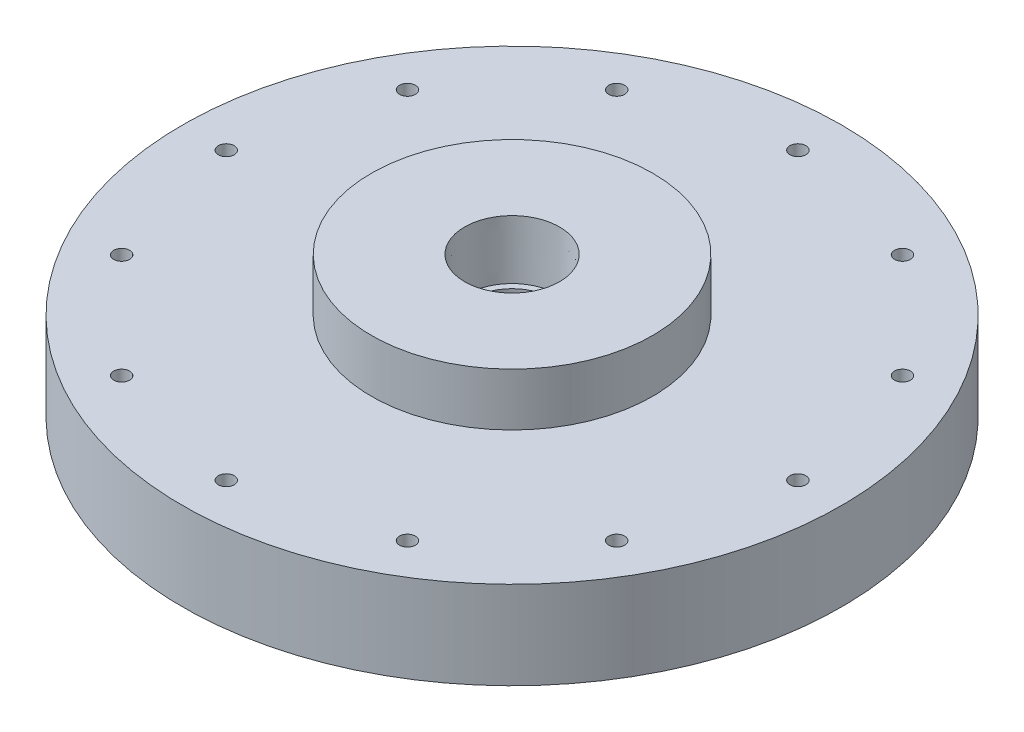
SolidWorks part; units mm, degrees
material "7075-T6 (SN)"
ref_plane "Front Plane" through (0, 0, 0) normal (0, 0, 1) x (1, 0, 0)
ref_plane "Top Plane" through (0, 0, 0) normal (0, 1, 0) x (1, 0, 0)
ref_plane "Right Plane" through (0, 0, 0) normal (1, 0, 0) x (0, 0, -1)
sketch "Sketch2" plane through (0, 0, 0) normal (0, 1, 0) x (1, 0, 0)
  circle A1 centre (0, 0) radius 25.4
  dimension "D1" = 50.8
extrude "Base Cylinder" add sketch "Sketch2" along normal blind 19.05
sketch "Sketch3" plane through (0, 0, 0) normal (0, -1, 0) x (1, 0, 0)
  circle A1 centre (0, 0) radius 59.5312
  dimension "D1" = 119.0625
extrude "Aft Flange" add sketch "Sketch3" against normal blind 9.525
sketch "Sketch For Bolt Holes" plane through (0, 0, 0) normal (0, -1, 0) x (1, 0, 0)
  circle A0 centre (-51.6255, 0) radius 1.5875
  circle A1 centre (-44.709, 25.8128) radius 1.5875
  circle A2 centre (-25.8128, 44.709) radius 1.5875
  circle A3 centre (0, 51.6255) radius 1.5875
  circle A4 centre (25.8127, 44.709) radius 1.5875
  circle A5 centre (44.709, 25.8128) radius 1.5875
  circle A6 centre (51.6255, 0) radius 1.5875
  circle A7 centre (44.709, -25.8127) radius 1.5875
  circle A8 centre (25.8128, -44.709) radius 1.5875
  circle A9 centre (0, -51.6255) radius 1.5875
  circle A10 centre (-25.8127, -44.709) radius 1.5875
  circle A11 centre (-44.709, -25.8128) radius 1.5875
  point P36 (0, 0)
  dimension "D2" = 3.175
  dimension "D1" = 51.6255
  dimension "D3" = 12
hole_wizard "Bolt Circle" positions "Sketch8" profile "Sketch9" hole size "#4-40" standard "ANSI Inch" end condition up to next
sketch "Sketch8" plane through (0, 0, 0) normal (0, -1, 0) x (-1, 0, 0)
  point P0 (-25.8127, -44.709)
  point P3 (-44.709, -25.8128)
  point P6 (-51.6255, 0)
  point P9 (-44.709, 25.8127)
  point P12 (-25.8128, 44.709)
  point P15 (0, 51.6255)
  point P18 (25.8127, 44.709)
  point P21 (44.709, 25.8128)
  point P24 (51.6255, 0)
  point P27 (44.709, -25.8128)
  point P30 (25.8128, -44.709)
  point P33 (0, -51.6255)
  point P36 (-25.8127, -44.709)
  point P38 (-44.709, -25.8128)
  point P40 (-51.6255, 0)
sketch "Sketch9" plane through (25.8127, 0, 44.709) normal (1, 0, 0) x (0, 0, -1)
  line L0 (0, 0) -> (0, 9.525)
  line L1 (0, 9.525) -> (1.4351, 9.525)
  line L2 (1.4351, 9.525) -> (1.4351, 0)
  line L5 (1.4351, 0) -> (0, 0)
  line L11 (0, -6.35) -> (0, 107.95) construction
  dimension "Thru Hole Dia." = 2.8702
  dimension "Thru Hole Depth" = 9.525
sketch "Dowel Hole Sketch" plane through (0, 0, 0) normal (0, -1, 0) x (1, 0, 0)
  line L0 (0, 0) -> (-51.6255, 0) construction
  line L1 (0, 0) -> (-49.8664, -13.3617) construction
  line L2 (0, 0) -> (0, -51.6255) construction
  line L3 (0, 0) -> (49.8664, 13.3617) construction
  circle A0 centre (0, 0) radius 51.6255
  circle A1 centre (-49.8664, -13.3617) radius 4.6172
  circle A2 centre (49.8664, 13.3617) radius 3.4532
  dimension "D1" = 15
ref_plane "Hoop Mid-Plane" through (0, 190.5, 0) normal (0, 1, 0) x (1, 0, 0)
sketch "Sketch15" plane through (0, 19.05, 0) normal (0, 1, 0) x (1, 0, 0)
  circle A0 centre (0, 0) radius 7.1106
hole_wizard "3/8 NPT Tapped Hole1" positions "Sketch16" profile "Sketch17" size "3/8" standard "ANSI Inch"
sketch "Sketch16" plane through (0, 19.05, 0) normal (0, 1, 0) x (1, 0, 0)
  point P0 (0, 0)
sketch "Sketch17" plane through (0, 19.05, 0) normal (1, 0, 0) x (0, 0, 1)
  line L0 (0, 0) -> (0, 21.8146)
  line L1 (7.1374, 17.526) -> (0, 21.8146)
  line L2 (-7.1374, 17.526) -> (0, 21.8146) construction
  line L3 (7.1374, 17.526) -> (7.1374, 10.414)
  line L4 (7.1374, 10.414) -> (8.2632, 10.414)
  line L5 (8.2632, 10.414) -> (8.575, 0)
  line L6 (-8.2632, 10.414) -> (-8.575, 0) construction
  line L7 (8.575, 0) -> (0, 0)
  line L8 (0, -6.35) -> (0, 107.95) construction
  line L11 (-7.1374, 10.414) -> (-8.2632, 10.414) construction
  dimension "Tap Drill Dia." = 14.2748
  dimension "Tap Drill Depth" = 17.526
  dimension "Thread Dia." = 17.15
  dimension "Thread Angle" = 3.43
  dimension "Thread Depth" = 10.414
  dimension "Drill Angle" = 118
sketch "Sketch18" plane through (0, 0, 0) normal (0, -1, 0) x (1, 0, 0)
  circle A0 centre (0, 0) radius 59.5312
extrude "Boss-Extrude1" add sketch "Sketch18" along normal blind 6.35
sketch "Sketch19" plane through (0, -6.35, 0) normal (0, -1, 0) x (1, 0, 0)
  circle A3 centre (0, 0) radius 56.4134
  dimension "D1" = 112.8268
extrude "Cut-Extrude1" cut sketch "Sketch19" against normal blind 6.35
